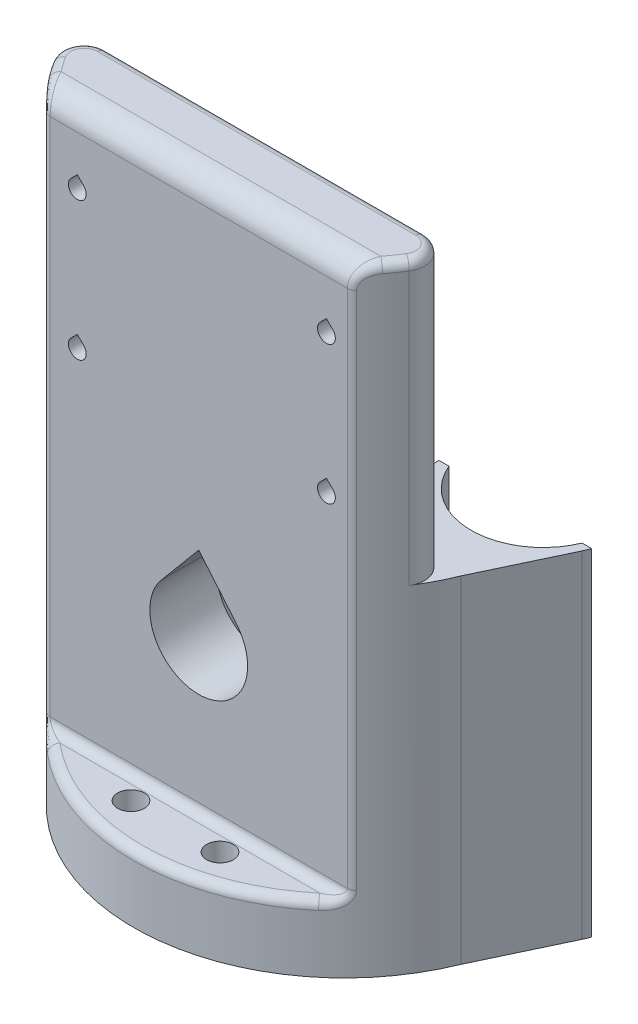
SolidWorks part; units mm, degrees
ref_plane "Front Plane" through (0, 0, 0) normal (0, 0, 1) x (1, 0, 0)
ref_plane "Top Plane" through (0, 0, 0) normal (0, 1, 0) x (1, 0, 0)
ref_plane "Right Plane" through (0, 0, 0) normal (1, 0, 0) x (0, 0, -1)
sketch "Sketch3" plane through (0, 0, 0) normal (0, 1, 0) x (1, 0, 0)
  line L0 (-43.9425, -17.7712) -> (43.9425, -17.7712)
  line L1 (-34.2463, -32.7712) -> (34.2463, -32.7712)
  arc A0 (-43.9425, -17.7712) -> (-34.2463, -32.7712) centre (0, 0) ccw
  arc A1 (34.2463, -32.7712) -> (43.9425, -17.7712) centre (0, 0) ccw
  dimension "D1" = 47.4
  dimension "D2" = 17.7712
  dimension "D3" = 15
extrude "Boss-Extrude2" add sketch "Sketch3" along normal blind 138.8
sketch "Sketch4" plane through (0, 0, 0) normal (0, 1, 0) x (1, 0, 0)
  line L0 (43.9425, -17.7712) -> (-43.9425, -17.7712) construction
  line L1 (0, -17.7712) -> (0, 19.754) construction
  line L2 (-36.2, 8.4288) -> (36.2, 8.4288) construction
  line L3 (-43.9425, -17.7712) -> (-52.653, 0.6482)
  line L7 (-43.9425, -17.7712) -> (-19, -17.7712)
  line L9 (-51.1666, 2.2288) -> (-53.3114, 2.2288)
  line L11 (51.1666, 2.2288) -> (53.3114, 2.2288)
  line L12 (-21.2334, 2.2288) -> (-19, 2.2288)
  line L13 (19, 2.2288) -> (21.2334, 2.2288)
  line L14 (19, 2.2288) -> (19, -17.7712)
  line L15 (-19, 2.2288) -> (-19, -17.7712)
  line L16 (19, -17.7712) -> (-43.9425, -17.7712)
  line L17 (52.653, 0.6482) -> (43.9425, -17.7712)
  line L18 (43.9425, -17.7712) -> (19, -17.7712)
  arc A0 (52.653, 0.6482) -> (53.3114, 2.2288) centre (36.2, 8.4288) ccw
  arc A1 (-53.3114, 2.2288) -> (-52.653, 0.6482) centre (-36.2, 8.4288) ccw
  arc A2 (-51.1666, 2.2288) -> (-21.2334, 2.2288) centre (-36.2, 8.4288) ccw
  arc A3 (21.2334, 2.2288) -> (51.1666, 2.2288) centre (36.2, 8.4288) ccw
  circle A4 centre (36.2, 8.4288) radius 18.2 construction
  circle A5 centre (-36.2, 8.4288) radius 18.2 construction
  circle A6 centre (36.2, 8.4288) radius 16.2 construction
  circle A7 centre (-36.2, 8.4288) radius 16.2 construction
  point P8 (0, 8.4288)
  point P11 (0, 0)
  point P16 (0, 0)
  point P32 (0, 0)
  point P33 (0, 0)
  point P34 (0, 0)
  point P36 (52.653, 0.6482)
  dimension "D3" = 2
  dimension "D4" = 32.4
  dimension "D5" = 20
  dimension "D1" = 26.2
  dimension "D2" = 72.4
extrude "Boss-Extrude4" add sketch "Sketch4" along normal blind 75.6 contours L3 A1 L9 A2 L12 L15 L7 | L14 L13 A3 L11 A0 L17 L18
sketch "Sketch5" plane through (0, 0, 32.7712) normal (0, 0, 1) x (1, 0, 0)
  line L0 (0, 138.8) -> (0, 0) construction
  line L1 (-34.2463, 138.8) -> (34.2463, 138.8) construction
  line L2 (-34.2463, 0) -> (34.2463, 0) construction
  line L3 (-28.7092, 124.1442) -> (-27.295, 125.5584)
  line L4 (-27.295, 125.5584) -> (-25.8808, 124.1442)
  line L5 (-28.7092, 124.1442) -> (-27.8569, 124.1442) construction
  line L6 (27.2808, 124.1442) -> (28.695, 125.5584)
  line L7 (28.695, 125.5584) -> (30.1092, 124.1442)
  line L8 (27.2808, 124.1442) -> (27.8245, 124.1442) construction
  line L9 (-28.7092, 93.0742) -> (-27.295, 94.4884)
  line L10 (-27.295, 94.4884) -> (-25.8808, 93.0742)
  line L11 (-28.7092, 93.0742) -> (-27.911, 93.0742) construction
  line L12 (27.2808, 93.0742) -> (28.695, 94.4884)
  line L13 (28.695, 94.4884) -> (30.1092, 93.0742)
  line L14 (27.2808, 93.0742) -> (27.9465, 93.0742) construction
  arc A0 (-28.7092, 124.1442) -> (-25.8808, 124.1442) centre (-27.295, 122.73) ccw
  arc A1 (27.2808, 124.1442) -> (30.1092, 124.1442) centre (28.695, 122.73) ccw
  arc A2 (-28.7092, 93.0742) -> (-25.8808, 93.0742) centre (-27.295, 91.66) ccw
  arc A3 (27.2808, 93.0742) -> (30.1092, 93.0742) centre (28.695, 91.66) ccw
  point P23 (0, 0)
  dimension "D1" = 4
  dimension "D4" = 31.07
  dimension "D2" = 55.99
  dimension "D3" = 27.295
  dimension "D5" = 16.07
  dimension "D6" = 45
  dimension "D7" = 45
  dimension "D8" = 45
  dimension "D9" = 45
extrude "Cut-Extrude2" cut sketch "Sketch5" against normal up to next
sketch "Sketch6" plane through (0, 0, 0) normal (0, -1, 0) x (1, 0, 0)
  line L0 (-34.2463, 32.7712) -> (34.2463, 32.7712)
  line L1 (-19, 17.7712) -> (19, 17.7712)
  line L2 (19, 17.7712) -> (19, -2.2288)
  line L3 (19, -2.2288) -> (19, 17.7712) construction
  line L4 (19, -2.2288) -> (-19, -2.2288)
  line L5 (-19, -2.2288) -> (-19, 17.7712) construction
  line L6 (-19, -2.2288) -> (-19, 17.7712)
  arc A0 (34.2463, 32.7712) -> (-34.2463, 32.7712) centre (0, 0) ccw
  arc A1 (43.9425, 17.7712) -> (34.2463, 32.7712) centre (0, 0) ccw construction
  point P11 (-19, 6.138)
  point P20 (-19, -2.2288)
extrude "Boss-Extrude5" add sketch "Sketch6" against normal blind 15
sketch "Sketch7" plane through (0, 15, 0) normal (0, 1, 0) x (1, 0, 0)
  circle A0 centre (-10, -38) radius 2
  circle A1 centre (10, -38) radius 2
  circle A2 centre (-10, -5) radius 2
  circle A3 centre (10, -5) radius 2
  point P8 (0, 0)
  point P9 (0, 0)
  point P10 (0, 0)
  point P12 (-10, -38.9759)
  point P13 (0, 0)
  dimension "D1" = 4
  dimension "D2" = 10
  dimension "D3" = 10
  dimension "D4" = 5
  dimension "D5" = 38
extrude "Cut-Extrude3" cut sketch "Sketch7" against normal blind 15
sketch "Sketch8" plane through (0, 15, 0) normal (0, 1, 0) x (1, 0, 0)
  circle A0 centre (10, -38) radius 3
  circle A1 centre (-10, -38) radius 3
  circle A2 centre (-10, -5) radius 3
  circle A3 centre (10, -5) radius 3
  dimension "D1" = 6
extrude "Cut-Extrude4" cut sketch "Sketch8" against normal blind 7.5
sketch "Sketch9" plane through (0, 0, 17.7712) normal (0, 0, -1) x (-1, 0, 0)
  line L0 (-8.4174, 56.1132) -> (0, 66.1446)
  line L5 (0, 66.1446) -> (8.4174, 56.1132)
  line L6 (-8.8623, 55.5461) -> (-3.8891, 55.5461) construction
  arc A0 (-8.4174, 56.1132) -> (8.4174, 56.1132) centre (0, 49.0501) ccw
  point P6 (0, 0)
  dimension "D1" = 50
extrude "Cut-Extrude5" cut sketch "Sketch9" against normal up to next
fillet "Fillet2" radius 5 1 edges at (0, 138.8, 32.7712)
fillet "Fillet3" radius 5 2 edges at (-43.9425, 107.2, 17.7712) (43.9425, 107.2, 17.7712)
fillet "Fillet6" radius 2 11 edges at (0, 15, 32.7712) (0, 15, 47.4) (0, 138.8, 17.7712) (-40.1497, 138.8, 20.3656) (40.1497, 138.8, 20.3656) (-39.2154, 138.8, 26.6254) (39.2154, 138.8, 26.6254) (-34.8835, 136.3159, 32.0921) (35.4216, 137.1343, 31.4971) (-34.2463, 74.4, 32.7712) (34.2463, 74.4, 32.7712)
fillet "Fillet7" radius 2 2 edges at (0, 15, -2.2288) (0, 15, 17.7712)
fillet "Fillet8" radius 2 8 edges at (19, 14.4142, -1.6431) (19, 46.3, 17.7712) (19, 15.5858, 17.1854) (-19, 46.3, 17.7712) (-19, 15.5858, 17.1854) (-19, 14.4142, -1.6431) (19, 15, 7.7712) (-19, 15, 7.7712)
equation "\"D3@Sketch7\"=\"D2@Sketch7\""
